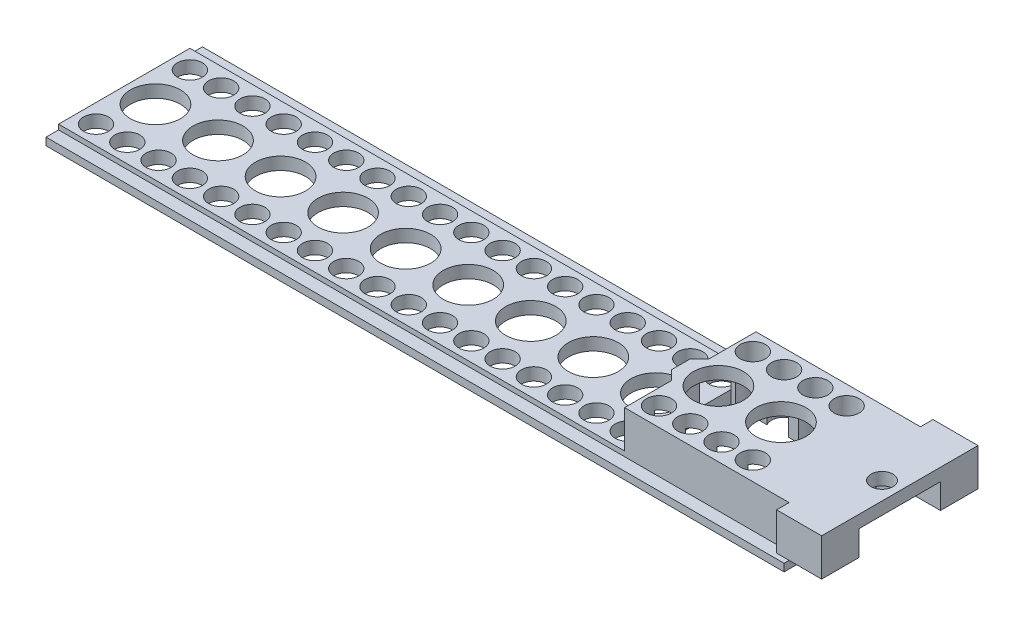
SolidWorks part; units mm, degrees
ref_plane "Ebene vorne" through (0, 0, 0) normal (0, 0, 1) x (1, 0, 0)
ref_plane "Ebene oben" through (0, 0, 0) normal (0, 1, 0) x (1, 0, 0)
ref_plane "Ebene rechts" through (0, 0, 0) normal (1, 0, 0) x (0, 0, -1)
sketch "Skizze1" plane through (0, 0, 0) normal (1, 0, 0) x (0, 0, -1)
  line L1 (-40.6559, -25.3697) -> (-15.6559, -25.3697)
  line L2 (-40.6559, -25.3697) -> (-40.6559, -33.3697)
  line L3 (-40.6559, -33.3697) -> (-15.6559, -33.3697)
  line L4 (-15.6559, -25.3697) -> (-15.6559, -33.3697)
  dimension "D1" = 8
  dimension "D2" = 25
extrude "Aufsatz-Linear austragen1" add sketch "Skizze1" along normal blind 124
sketch "Skizze2" plane through (0, 0, 0) normal (-1, 0, 0) x (0, 0, 1)
  line L0 (40.6559, -33.3697) -> (15.6559, -33.3697) construction
  line L1 (15.6559, -25.3697) -> (17.6559, -25.3697)
  line L2 (15.6559, -25.3697) -> (15.6559, -32.1697)
  line L3 (15.6559, -32.1697) -> (17.6559, -32.1697)
  line L4 (17.6559, -25.3697) -> (17.6559, -32.1697)
  line L5 (40.6559, -25.3697) -> (38.6559, -25.3697)
  line L6 (40.6559, -25.3697) -> (40.6559, -32.1697)
  line L7 (40.6559, -32.1697) -> (38.6559, -32.1697)
  line L8 (38.6559, -25.3697) -> (38.6559, -32.1697)
  line L9 (15.6559, -33.3697) -> (15.6559, -25.3697) construction
  line L10 (15.6559, -25.3697) -> (40.6559, -25.3697) construction
  dimension "D1" = 2
  dimension "D2" = 0
  dimension "D3" = 2
  dimension "D4" = 1.2
  dimension "D5" = 0
  dimension "D6" = 1.2
extrude "Schnitt-Linear austragen1" cut sketch "Skizze2" against normal through all
sketch "Skizze3" plane through (0, -25.3697, 0) normal (0, 1, 0) x (1, 0, 0)
  line L0 (124, -17.6559) -> (124, -38.6559) construction
  line L1 (124, -21.6559) -> (118, -21.6559)
  line L2 (124, -21.6559) -> (124, -15.6559)
  line L3 (124, -15.6559) -> (118, -15.6559)
  line L4 (118, -21.6559) -> (118, -15.6559)
  line L5 (124, -15.6559) -> (0, -15.6559) construction
  line L6 (124, -40.6559) -> (0, -40.6559) construction
  line L7 (124, -34.6559) -> (118, -34.6559)
  line L8 (124, -34.6559) -> (124, -40.6559)
  line L9 (124, -40.6559) -> (118, -40.6559)
  line L10 (118, -34.6559) -> (118, -40.6559)
  circle A0 centre (121.15, -28.1559) radius 1.75
  dimension "D6" = 3.5
  dimension "D7" = 2.85
  dimension "D1" = 12.5
  dimension "D2" = 6
  dimension "D3" = 0
  dimension "D4" = 6
  dimension "D5" = 6
extrude "Schnitt-Linear austragen2" cut sketch "Skizze3" against normal through all
sketch "Skizze4" plane through (118, 0, 0) normal (1, 0, 0) x (0, 0, -1)
  line L0 (-34.6559, -33.3697) -> (-34.6559, -25.3697) construction
  line L1 (-38.6559, -25.3697) -> (-34.6559, -25.3697)
  line L2 (-38.6559, -25.3697) -> (-38.6559, -32.1697)
  line L3 (-38.6559, -32.1697) -> (-34.6559, -32.1697)
  line L4 (-34.6559, -25.3697) -> (-34.6559, -32.1697)
  line L5 (-21.6559, -33.3697) -> (-21.6559, -25.3697) construction
  line L6 (-17.6559, -25.3697) -> (-21.6559, -25.3697)
  line L7 (-17.6559, -25.3697) -> (-17.6559, -32.1697)
  line L8 (-17.6559, -32.1697) -> (-21.6559, -32.1697)
  line L9 (-21.6559, -25.3697) -> (-21.6559, -32.1697)
  line L10 (-40.6559, -32.1697) -> (-38.6559, -32.1697) construction
  line L11 (-17.6559, -32.1697) -> (-15.6559, -32.1697) construction
  dimension "D1" = 0
  dimension "D2" = 0
extrude "Schnitt-Linear austragen3" cut sketch "Skizze4" against normal blind 1.2
sketch "Skizze5" plane through (0, -25.3697, 0) normal (0, 1, 0) x (1, 0, 0)
  line L0 (116.8, -17.6559) -> (0, -17.6559) construction
  line L1 (116.8, -38.6559) -> (0, -38.6559) construction
  line L2 (0, -17.6559) -> (0, -38.6559) construction
  circle A0 centre (3, -20.6559) radius 2
  circle A1 centre (5, -28.1559) radius 4
  circle A2 centre (3, -35.6559) radius 2
  circle A3 centre (8, -35.6559) radius 2
  circle A4 centre (8, -20.6559) radius 2
  dimension "D4" = 4
  dimension "D6" = 4
  dimension "D8" = 8
  dimension "D10" = 4
  dimension "D11" = 4
  dimension "D1" = 3
  dimension "D2" = 3
  dimension "D3" = 3
  dimension "D5" = 7.5
  dimension "D7" = 3
  dimension "D9" = 5
  dimension "D12" = 5
  dimension "D13" = 5
extrude "Schnitt-Linear austragen4" cut sketch "Skizze5" against normal through all
pattern_linear "Lineares Muster1" count 11 spacing 10 along (1, 0, 0) of "Schnitt-Linear austragen4"
sketch "Skizze6" plane through (0, -25.3697, 0) normal (0, 1, 0) x (1, 0, 0)
  line L0 (116.8, -38.6559) -> (0, -38.6559) construction
  line L1 (0, -17.6559) -> (90.5, -17.6559)
  line L2 (0, -17.6559) -> (0, -38.6559)
  line L3 (0, -38.6559) -> (90.5, -38.6559)
  line L4 (90.5, -17.6559) -> (90.5, -38.6559)
  line L5 (124, -21.6559) -> (124, -34.6559) construction
  dimension "D1" = 33.5
extrude "Schnitt-Linear austragen5" cut sketch "Skizze6" against normal blind 6
sketch "Skizze7" plane through (0, -33.3697, 0) normal (0, -1, 0) x (1, 0, 0)
  line L0 (124, 34.6559) -> (118, 34.6559) construction
  line L1 (124, 34.6559) -> (90.5, 34.6559)
  line L2 (124, 34.6559) -> (124, 21.6559)
  line L3 (124, 21.6559) -> (90.5, 21.6559)
  line L4 (90.5, 34.6559) -> (90.5, 21.6559)
  line L5 (118, 21.6559) -> (124, 21.6559) construction
  line L8 (90.5, 38.6559) -> (90.5, 17.6559) construction
  line L9 (124, 34.6559) -> (124, 21.6559) construction
  dimension "D1" = 0
  dimension "D2" = 0
  dimension "D3" = 0
  dimension "D4" = 0
extrude "Schnitt-Linear austragen6" cut sketch "Skizze7" against normal blind 6
sketch "Skizze8" plane through (0, -25.3697, 0) normal (0, 1, 0) x (1, 0, 0)
  line L0 (118, -15.6559) -> (0, -15.6559) construction
  line L1 (116.8, -21.6559) -> (124, -21.6559)
  line L2 (116.8, -21.6559) -> (116.8, -15.6559)
  line L3 (116.8, -15.6559) -> (124, -15.6559)
  line L4 (124, -21.6559) -> (124, -15.6559)
  line L5 (116.8, -34.6559) -> (124, -34.6559)
  line L6 (116.8, -34.6559) -> (116.8, -40.6559)
  line L7 (116.8, -40.6559) -> (124, -40.6559)
  line L8 (124, -34.6559) -> (124, -40.6559)
  line L9 (124, -21.6559) -> (124, -34.6559) construction
  line L10 (118, -40.6559) -> (0, -40.6559) construction
  dimension "D1" = 0
  dimension "D2" = 0
  dimension "D3" = 0
  dimension "D4" = 0
extrude "Aufsatz-Linear austragen2" add sketch "Skizze8" against normal blind 6
sketch "Skizze9" plane through (0, -31.3697, 0) normal (0, 1, 0) x (1, 0, 0)
  line L0 (90.5, -34.6559) -> (90.5, -21.6559) construction
  line L1 (90.5, -26.6559) -> (89, -26.6559)
  line L2 (90.5, -26.6559) -> (90.5, -29.6559)
  line L3 (90.5, -29.6559) -> (89, -29.6559)
  line L4 (89, -26.6559) -> (89, -29.6559)
  line L5 (90.5, -17.6559) -> (0, -17.6559) construction
  line L6 (0, -38.6559) -> (90.5, -38.6559) construction
  circle A0 centre (85, -28.1559) radius 4 construction
  dimension "D1" = 4
  dimension "D2" = 9
  dimension "D3" = 9
extrude "Aufsatz-Linear austragen3" add sketch "Skizze9" along normal up to surface (6 mm away) up to face at (112.025, -25.3697, 28.1559)
chamfer "Fase1" distance 1.5 angle 45 2 edges at (90.5, -26.3697, 29.6559) (90.5, -26.3697, 26.6559)
